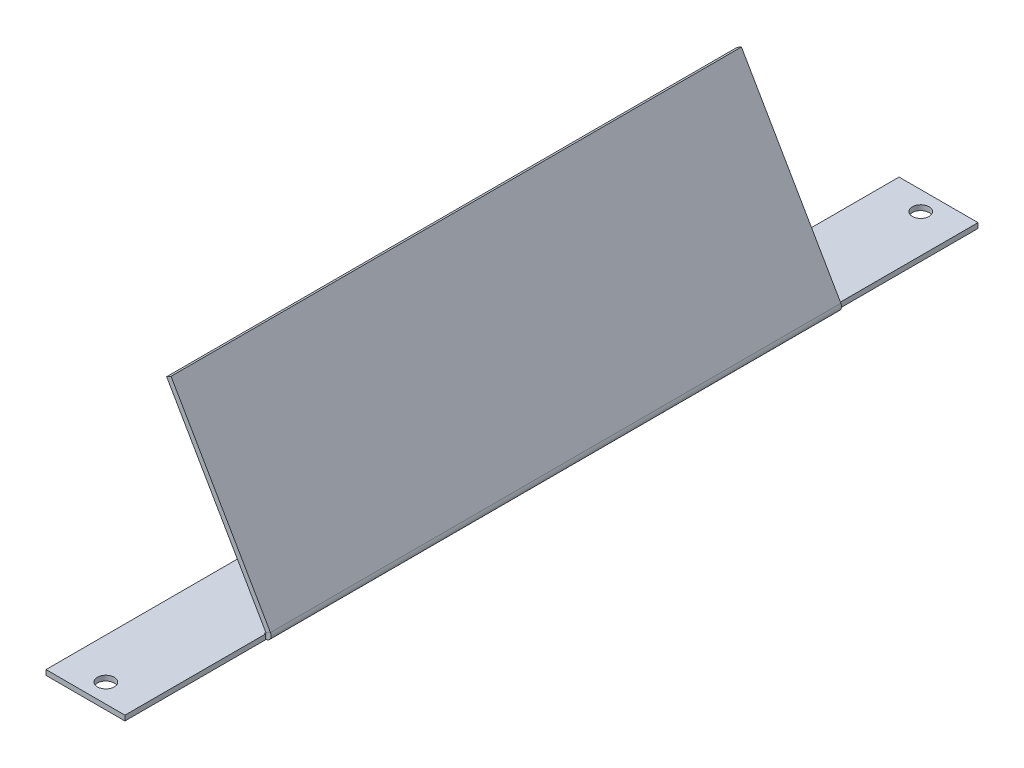
SolidWorks part; units mm, degrees
note: The reader was unsure of these and kept them because the rebuilt part matched: flange length of "Kante-Lasche1".
material "1.4301 (X5CrNi18-10)"
ref_plane "Vorne" through (0, 0, 0) normal (0, 0, 1) x (1, 0, 0)
ref_plane "Oben" through (0, 0, 0) normal (0, 1, 0) x (1, 0, 0)
ref_plane "Rechts" through (0, 0, 0) normal (1, 0, 0) x (0, 0, -1)
sketch "Skizze2" plane through (0, 0, 0) normal (0, 1, 0) x (1, 0, 0)
  line L1 (-175, 167.5) -> (175, 167.5)
  line L2 (-175, 167.5) -> (-175, -167.5)
  line L3 (-175, -167.5) -> (175, -167.5)
  line L4 (175, 167.5) -> (175, -167.5)
  line L5 (-175, 167.5) -> (175, -167.5) construction
  line L6 (-175, -167.5) -> (175, 167.5) construction
  point P0 (0, 0)
  dimension "D1" = 350
  dimension "D2" = 335
sheet metal parameters "Blech1" thickness 2 parameters "D1"=0.1
sheet metal parameters "Blech2" thickness 2 parameters "D1"=0.1, "Dicke"=2
base flange "Basis-Blech1" sketch "Skizze2" thickness 2 reverse thickness direction no parameters "D1"=0.1
edge flange "Kante-Lasche1" sketch "Skizze22" flange angle 60 flange length 78.2679 flange position material outside bend radius 0.1 thickness 2 relief rectangular parameters "D6"=10
sketch "Skizze22" plane through (175, 0, 0) normal (0.866, 0.5, 0) x (0, 0, -1)
  line L0 (-167.5, 0) -> (167.5, 0) construction
  line L1 (-112, 0) -> (112, 0)
  line L2 (-112, 0) -> (-112, 78.2679)
  line L3 (-112, 78.2679) -> (112, 78.2679)
  line L4 (112, 78.2679) -> (112, 0)
  line L6 (-167.5, -1.7321) -> (167.5, -1.7321) construction
  point P8 (0, 0)
  dimension "D1" = 224
  dimension "D2" = 80
bend "Kantenbiegung1" bend radius 0.1 bend angle 120 parameters "D5"=1
hole_wizard "Durchgangsloch für M61" positions "Skizze27" profile "Skizze26" hole size "M6" standard "Gabler-Normteile"
sketch "Skizze27" plane through (0, -2, 0) normal (0, -1, 0) x (-1, 0, 0)
  line L0 (0, 0) -> (0, 105.8498) construction
  line L1 (-175, 167.5) -> (175, 167.5) construction
  line L2 (175, -167.5) -> (-175, -167.5) construction
  line L3 (175, 167.5) -> (175, -167.5) construction
  line L4 (-175, 112.3) -> (-175, 167.5) construction
  point P0 (-160, -160)
  point P2 (160, -160)
  point P15 (160, 160)
  point P17 (-160, 160)
  dimension "D1" = 7.5
  dimension "D2" = 7.5
  dimension "D3" = 15
  dimension "D4" = 15
sketch "Skizze26" plane through (160, -2, 160) normal (1, 0, 0) x (0, 0, -1)
  line L0 (0, 0) -> (0, 16.9828)
  line L1 (0, 16.9828) -> (3.3, 15)
  line L2 (3.3, 15) -> (3.3, 0)
  line L5 (3.3, 0) -> (0, 0)
  line L10 (0, 16.9828) -> (-3.3, 15) construction
  line L11 (0, -6.35) -> (0, 107.95) construction
  dimension "Bohrerdurchmesser" = 6.6
  dimension "Bohrungstiefe" = 15
  dimension "Spitzenwinkel" = 118
hole_wizard "Durchgangsloch für M121" positions "Skizze29" profile "Skizze28" hole size "M12" standard "Gabler-Normteile" end condition through all
sketch "Skizze29" plane through (0, 0, 0) normal (0, 1, 0) x (1, 0, 0)
  line L0 (175, 167.5) -> (-175, 167.5) construction
  line L1 (-175, -167.5) -> (175, -167.5) construction
  line L2 (-175, 167.5) -> (-175, -167.5) construction
  point P0 (-25, 145.5)
  point P2 (-25, -145.5)
  dimension "D1" = 22
  dimension "D2" = 22
  dimension "D3" = 150
sketch "Skizze28" plane through (-25, 0, -145.5) normal (1, 0, 0) x (0, 0, 1)
  line L0 (0, 0) -> (0, 2)
  line L1 (0, 2) -> (6.75, 2)
  line L2 (6.75, 2) -> (6.75, 0)
  line L5 (6.75, 0) -> (0, 0)
  line L11 (0, -6.35) -> (0, 107.95) construction
  dimension "Bohrerdurchmesser" = 13.5
  dimension "Bohrungstiefe" = 2
sketch "Skizze30" plane through (0, -2, 0) normal (0, -1, 0) x (1, 0, 0)
  line L1 (-175, 167.5) -> (144, 167.5)
  line L2 (-175, 167.5) -> (-175, -167.5)
  line L3 (-175, -167.5) -> (144, -167.5)
  line L4 (144, 167.5) -> (144, -167.5)
  line L5 (-175, -167.5) -> (-175, 167.5) construction
  line L7 (-175, 167.5) -> (175, 167.5) construction
  line L8 (175, -167.5) -> (-175, -167.5) construction
  line L10 (175, 167.5) -> (175, 112.3) construction
  circle A0 centre (160, 160) radius 3.3 construction
  point P26 (0, 0)
  dimension "D1" = 16
  dimension "D2" = 31
extrude "Schnitt-Linear austragen1" cut sketch "Skizze30" against normal blind 10 normal cut yes
bend "AbgeleiteteBiegung1" bend radius 0.1 bend angle 120 parameters "D5"=1
flat pattern "Abwicklung1" [suppressed]
sketch "Biegung-Linien1" plane through (0, -2, 0) normal (0, -1, 0) x (1, 0, 0)
  line L0 (175.2457, 112) -> (175.2457, -112) construction
  line L1 (175.2457, 112) -> (175.2457, -112) construction
sketch3d "Rahmen1" [suppressed]
  line L0 (-31, -335, 0) -> (-31, 0, 0) construction
  line L1 (62.4913, -335, 0) -> (62.4913, 0, 0) construction
  line L2 (-31, -335, 0) -> (62.4913, -335, 0) construction
  line L3 (-31, 0, 0) -> (62.4913, 0, 0) construction
bend of the flat pattern "Abwickeln-<Kantenbiegung1>1"
flat pattern "Abwicklung2" [suppressed]
sketch "Biegung-Linien2" plane through (0, 0, 0) normal (0, 1, 0) x (1, 0, 0)
sketch "Rahmen2" [suppressed] plane through (0, 0, 0) normal (0, 1, 0) x (1, 0, 0)
bend of the flat pattern "Abwickeln-<AbgeleiteteBiegung1>1"
